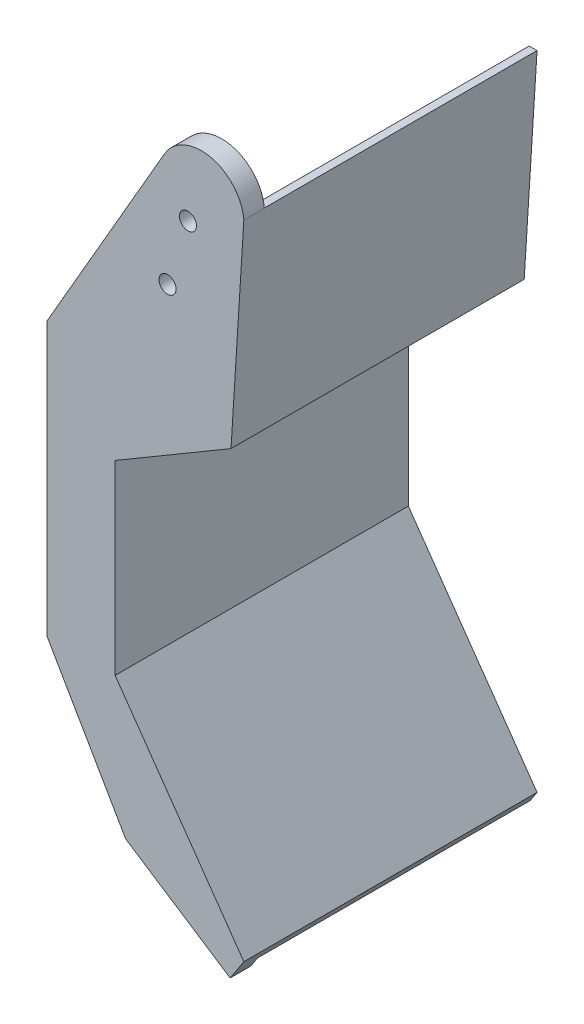
SolidWorks part; units mm, degrees
ref_plane "前视基准面" through (0, 0, 0) normal (0, 0, 1) x (1, 0, 0)
ref_plane "上视基准面" through (0, 0, 0) normal (0, 1, 0) x (1, 0, 0)
ref_plane "右视基准面" through (0, 0, 0) normal (1, 0, 0) x (0, 0, -1)
sketch "草图1" plane through (0, 0, 0) normal (0, 0, 1) x (1, 0, 0)
  line L0 (0.4413, 66.8945) -> (-16.8792, 36.8945)
  line L1 (-16.8792, 36.8945) -> (-16.8792, -3.1055)
  line L2 (-16.8792, -3.1055) -> (-5.3322, -23.1055)
  line L5 (-7.0008, 37.5151) -> (-6.8792, 37.579)
  line L26 (-5.3322, -23.1055) -> (9.9927, -33.1055)
  line L27 (11.9998, 64.1907) -> (10.1143, 34.1907)
  line L28 (10.1143, 34.1907) -> (-6.8792, 24.1907)
  line L29 (-6.8792, 24.1907) -> (-6.8792, 14.1907)
  line L32 (-6.8792, 14.1907) -> (-6.8792, -3.1055)
  line L35 (-6.8792, -3.1055) -> (11.9998, -30.0298)
  line L36 (11.9998, -30.0298) -> (9.9927, -33.1055)
  arc A4 (0.4413, 66.8945) -> (11.9998, 64.1907) centre (5.7669, 63.6033) cw
  dimension "D7" = 30
  dimension "D8" = 10
  dimension "D9" = 10
  dimension "D6" = 10
  dimension "D1" = 150
  dimension "D2" = 150
  dimension "D3" = 30
  dimension "D4" = 40
  dimension "D5" = 20
  dimension "D10" = 10
extrude "凸台-拉伸4" add sketch "草图1" along normal blind 3 contours A4 L0 L1 L2 L26 L36 L35 L32 L29 L28 L27 region at (6.9493, 68.6579, 0)
sketch "草图6" plane through (0, 0, 0) normal (0, 0, -1) x (-1, 0, 0)
  line L0 (6.8792, 24.1907) -> (8.2484, 24.1907)
  line L1 (8.2484, 24.1907) -> (8.2484, -3.1455)
  line L2 (8.2484, -3.1455) -> (-10.9962, -31.5677)
  line L3 (-11.9998, -30.0298) -> (-9.9927, -33.1055) construction
  line L13 (-11.9998, 64.1907) -> (-10.1143, 34.1907)
  line L14 (-10.1143, 34.1907) -> (6.8792, 24.1907)
  line L15 (6.8792, 24.1907) -> (6.8792, -3.1055)
  line L16 (6.8792, -3.1055) -> (-11.9998, -30.0298)
  line L17 (-11.9998, -30.0298) -> (-9.9927, -33.1055)
  line L18 (-9.9927, -33.1055) -> (5.3322, -23.1055)
  line L19 (5.3322, -23.1055) -> (16.8792, -3.1055)
  line L20 (16.8792, -3.1055) -> (16.8792, 36.8945)
  line L21 (16.8792, 36.8945) -> (-0.4413, 66.8945)
  line L24 (6.8792, 24.1907) -> (6.8792, -3.1055)
  line L25 (6.8792, -3.1055) -> (-11.9998, -30.0298)
  line L26 (-11.9998, -30.0298) -> (-10.9962, -31.5677)
  arc A1 (-0.4413, 66.8945) -> (-11.9998, 64.1907) centre (-5.7669, 63.6033) ccw
  dimension "D1" = 0
extrude "凸台-拉伸6" add sketch "草图6" along normal blind 40
sketch "草图7" plane through (0, 0, 0) normal (0, 0, -1) x (-1, 0, 0)
  line L0 (-10.1143, 34.1907) -> (6.8792, 24.1907)
  line L1 (6.8792, 24.1907) -> (8.2484, 24.1907)
  line L2 (8.2484, 24.1907) -> (8.2484, 25.7056)
  line L3 (8.2484, 25.7056) -> (-9.1, 35.9144)
  line L4 (-9.1, 35.9144) -> (-10.1143, 34.1907)
  line L5 (-35.8591, 35.3541) -> (-35.7166, 35.3541)
  dimension "D1" = 2
extrude "凸台-拉伸7" add sketch "草图7" along normal blind 40 contours L3 L4 L0 L1 L2
sketch "草图8" plane through (0, 0, 0) normal (0, 0, -1) x (-1, 0, 0)
  line L0 (-11.9998, 64.1907) -> (-10.844, 64.1907)
  line L1 (-10.844, 64.1907) -> (-9.1, 37.3813)
  line L2 (-9.1, 37.3813) -> (-9.6072, 35.0526)
  line L3 (-9.1, 35.9144) -> (-10.1143, 34.1907) construction
  line L14 (-9.1, 35.9144) -> (8.2484, 25.7056)
  line L15 (8.2484, 25.7056) -> (8.2484, -3.1455)
  line L16 (8.2484, -3.1455) -> (-10.9962, -31.5677)
  line L17 (-10.9962, -31.5677) -> (-9.9927, -33.1055)
  line L18 (-9.9927, -33.1055) -> (5.3322, -23.1055)
  line L19 (5.3322, -23.1055) -> (16.8792, -3.1055)
  line L20 (16.8792, -3.1055) -> (16.8792, 36.8945)
  line L21 (16.8792, 36.8945) -> (-0.4413, 66.8945)
  line L22 (-11.9998, 64.1907) -> (-10.1143, 34.1907)
  line L23 (-10.1143, 34.1907) -> (-9.1, 35.9144)
  line L32 (-11.9998, 64.1907) -> (-10.1143, 34.1907)
  line L33 (-10.1143, 34.1907) -> (-9.6072, 35.0526)
  arc A2 (-0.4413, 66.8945) -> (-11.9998, 64.1907) centre (-5.7669, 63.6033) ccw
  dimension "D1" = 0
extrude "凸台-拉伸8" add sketch "草图8" along normal blind 40
sketch "草图12" plane through (0, 0, 3) normal (0, 0, 1) x (1, 0, 0)
  circle A0 centre (3.8001, 59.9413) radius 1.25
  circle A1 centre (0.8055, 50.4002) radius 1.25
  dimension "D1" = 10
extrude "切除-拉伸1" cut sketch "草图12" against normal through all
